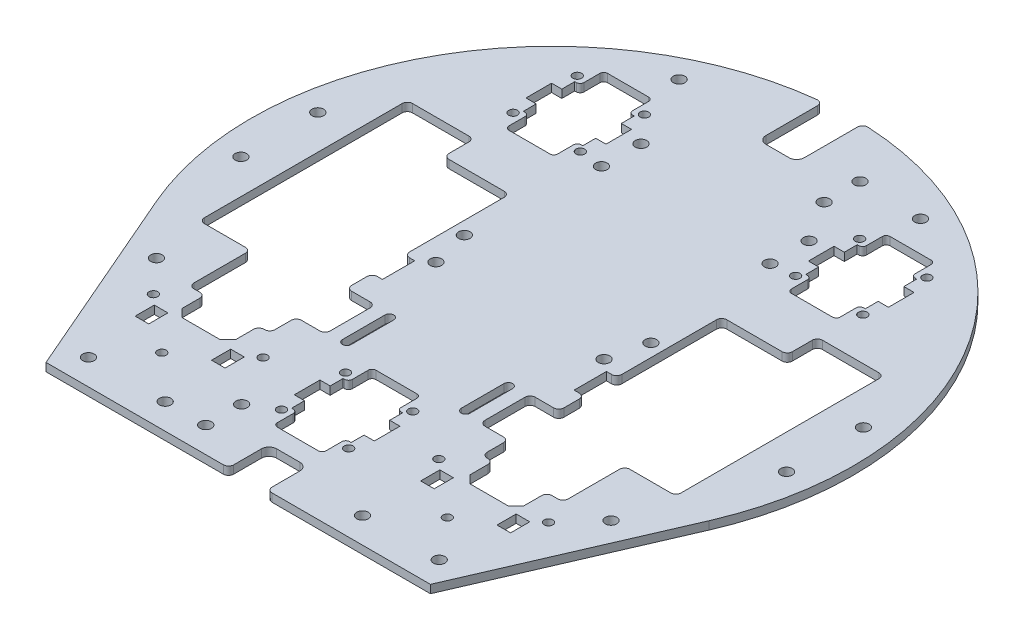
SolidWorks part; units mm, degrees
ref_plane "Front Plane" through (0, 0, 0) normal (0, 0, 1) x (1, 0, 0)
ref_plane "Top Plane" through (0, 0, 0) normal (0, 1, 0) x (1, 0, 0)
ref_plane "Right Plane" through (0, 0, 0) normal (1, 0, 0) x (0, 0, -1)
sketch "Sketch1" plane through (0, 0, 0) normal (0, 1, 0) x (1, 0, 0)
  circle A0 centre (0, 0) radius 117.5
  dimension "D1" = 235
extrude "Boss-Extrude1" add sketch "Sketch1" along normal blind 3.175
sketch "Sketch3" plane through (0, 0, 0) normal (0, 1, 0) x (1, 0, 0)
  line L3 (-107.8261, -46.6881) -> (-75, -122.5)
  line L5 (-75, -122.5) -> (75, -122.5)
  line L6 (75, -122.5) -> (107.8261, -46.6881)
  line L7 (107.8261, -46.6881) -> (-107.8261, -46.6881)
  line L8 (0, -122.5) -> (0, -117.5) construction
  circle A2 centre (0, 0) radius 117.5 construction
  dimension "D1" = 150
  dimension "D2" = 5
extrude "Boss-Extrude2" add sketch "Sketch3" along normal up to surface (3.175 mm away) up to face at (0, 3.175, 117.5)
sketch "Sketch4" plane through (0, 3.175, 0) normal (0, 1, 0) x (1, 0, 0)
  line L0 (70, 31.499) -> (70, -36.6986)
  line L1 (90, 31.499) -> (90, -36.6986)
  line L4 (93, 36.499) -> (67, 36.499)
  line L5 (90, -36.6986) -> (70, -36.6986) construction
  line L6 (67, 36.499) -> (67, 24.7405)
  line L7 (70, 31.499) -> (90, 31.499)
  line L8 (67, 24.7405) -> (41.4, 24.7405)
  line L9 (41.4, 24.7405) -> (41.4, -68.7747)
  line L10 (41.4, -68.7747) -> (73, -68.7747)
  line L11 (73, -68.7747) -> (73, -44.6986)
  line L12 (73, -44.6986) -> (93, -44.6986)
  line L13 (93, -44.6986) -> (93, 36.499)
  line L14 (46.4, 31.499) -> (89.2885, 31.499) construction
  line L15 (70, 31.499) -> (90, 31.499) construction
  line L19 (90, 31.499) -> (90, -36.6986) construction
  line L20 (70, 31.499) -> (70, -36.6986) construction
  line L22 (33.2, -41.8146) -> (33.2, -55.4255)
  line L24 (43.4, -41.8146) -> (33.2, -41.8146)
  line L25 (0, 0) -> (0, 30.6953) construction
  line L26 (-93, -44.6986) -> (-93, 36.499)
  line L27 (-73, -44.6986) -> (-93, -44.6986)
  line L28 (-73, -68.7747) -> (-73, -44.6986)
  line L29 (-41.4, -68.7747) -> (-73, -68.7747)
  line L30 (-41.4, 24.7405) -> (-41.4, -68.7747)
  line L31 (-67, 24.7405) -> (-41.4, 24.7405)
  line L32 (-67, 36.499) -> (-67, 24.7405)
  line L33 (-93, 36.499) -> (-67, 36.499)
  line L35 (33.2, -55.4255) -> (43.4, -55.4255) construction
  line L36 (39.4, -26.8239) -> (39.4, -18.2172)
  line L37 (39.4, -26.8239) -> (43.4, -26.8239)
  line L38 (43.4, -18.2172) -> (39.4, -18.2172)
  line L39 (68, 19.7405) -> (68, -67.7747)
  line L40 (68, -67.7747) -> (43.4, -67.7747)
  line L41 (43.4, 19.7405) -> (68, 19.7405)
  line L42 (43.4, 19.7405) -> (43.4, -18.2172)
  line L43 (43.4, -26.8239) -> (43.4, -41.8146)
  line L44 (43.4, -55.4255) -> (43.4, -67.7747)
  line L45 (43.4, -55.4255) -> (43.4, -67.7747) construction
  line L46 (43.4, -26.8239) -> (43.4, -41.8146) construction
  line L47 (43.4, 19.7405) -> (43.4, -18.2172) construction
  line L48 (43.4, 19.7405) -> (68, 19.7405) construction
  line L49 (68, -67.7747) -> (43.4, -67.7747) construction
  line L50 (68, 19.7405) -> (68, -67.7747) construction
  line L51 (43.4, -18.2172) -> (39.4, -18.2172) construction
  line L52 (39.4, -26.8239) -> (43.4, -26.8239) construction
  line L53 (39.4, -26.8239) -> (39.4, -18.2172) construction
  line L55 (43.4, -41.8146) -> (33.2, -41.8146) construction
  line L56 (33.2, -41.8146) -> (33.2, -55.4255) construction
  line L60 (33.2, -55.4255) -> (43.4, -55.4255)
  line L64 (90, -36.6986) -> (70, -36.6986)
  dimension "D1" = 2
  dimension "D2" = 5
  dimension "D3" = 5
  dimension "D4" = 8
  dimension "D5" = 3
  dimension "D6" = 5
  dimension "D7" = 5
  dimension "D8" = 3
  dimension "D9" = 2
extrude "Cut-Extrude1" cut sketch "Sketch4" against normal through all
sketch "Sketch8" plane through (0, 0, 0) normal (0, -1, 0) x (1, 0, 0)
  line L0 (-42, -78) -> (-68.225, -78) construction
  line L1 (13.1125, 12.5) -> (-13.1125, 12.5)
  line L2 (13.1125, 12.5) -> (13.1125, -12.5)
  line L3 (13.1125, -12.5) -> (-13.1125, -12.5)
  line L4 (-13.1125, 12.5) -> (-13.1125, -12.5)
  line L5 (13.1125, 12.5) -> (-13.1125, -12.5) construction
  line L6 (13.1125, -12.5) -> (-13.1125, 12.5) construction
  line L7 (-42, -53) -> (-42, -78) construction
  line L13 (0, 0) -> (0, -77.7063) construction
  line L14 (0, 80) -> (0, 0) construction
  line L15 (-42, -53) -> (-68.225, -53)
  line L16 (-42, -53) -> (-42, -78)
  line L17 (-42, -78) -> (-68.225, -78)
  line L18 (-68.225, -53) -> (-68.225, -78)
  line L19 (-42, -53) -> (-68.225, -78) construction
  line L20 (-42, -78) -> (-68.225, -53) construction
  line L21 (13.1125, 92.5) -> (-13.1125, 92.5)
  line L22 (13.1125, 92.5) -> (13.1125, 67.5)
  line L23 (13.1125, 67.5) -> (-13.1125, 67.5)
  line L24 (-13.1125, 92.5) -> (-13.1125, 67.5)
  line L25 (13.1125, 92.5) -> (-13.1125, 67.5) construction
  line L26 (13.1125, 67.5) -> (-13.1125, 92.5) construction
  line L27 (-42, -53) -> (-68.225, -53) construction
  line L28 (42, -78) -> (68.225, -78)
  line L29 (68.225, -53) -> (68.225, -78)
  line L30 (42, -78) -> (68.225, -53) construction
  line L31 (42, -53) -> (68.225, -78) construction
  line L32 (42, -53) -> (68.225, -53)
  line L33 (42, -53) -> (42, -78)
  point P0 (0, 0)
  point P15 (-55.1125, -65.5)
  point P20 (0, 80)
  point P29 (55.1125, -65.5)
  dimension "D1" = 42
  dimension "D2" = 80
hole_wizard "M3 Clearance Hole1" positions "Sketch9" profile "Sketch10" hole size "M3" standard "ANSI Metric" end condition through all
sketch "Sketch9" plane through (0, 3.175, 0) normal (0, 1, 0) x (1, 0, 0)
  point P0 (-68.225, 78)
  point P3 (-68.225, 53)
  point P6 (-42, 53)
  point P9 (-42, 78)
  point P12 (42, 78)
  point P15 (68.225, 78)
  point P18 (68.225, 53)
  point P21 (42, 53)
  point P24 (-13.1125, -67.5)
  point P27 (13.1125, -67.5)
  point P30 (13.1125, -92.5)
  point P33 (-13.1125, -92.5)
sketch "Sketch10" plane through (-68.225, 3.175, -78) normal (1, 0, 0) x (0, 0, 1)
  line L0 (0, 0) -> (0, 3.175)
  line L1 (0, 3.175) -> (1.7, 3.175)
  line L2 (1.7, 3.175) -> (1.7, 0)
  line L5 (1.7, 0) -> (0, 0)
  line L11 (0, -6.35) -> (0, 107.95) construction
  dimension "Thru Hole Dia." = 3.4
  dimension "Thru Hole Depth" = 3.175
sketch "Sketch11" plane through (0, 0, 0) normal (0, -1, 0) x (1, 0, 0)
  line L0 (47.6125, -48.2591) -> (62.6125, -48.2591)
  line L1 (62.6125, -82.7409) -> (47.6125, -82.7409)
  line L2 (62.6125, -82.7409) -> (47.6125, -82.7409)
  line L3 (47.6125, -48.2591) -> (62.6125, -48.2591)
  line L4 (-62.6125, -48.2591) -> (-47.6125, -48.2591)
  line L5 (-47.6125, -82.7409) -> (-62.6125, -82.7409)
  line L6 (-47.6125, -82.7409) -> (-62.6125, -82.7409)
  line L7 (-62.6125, -48.2591) -> (-47.6125, -48.2591)
  line L8 (-7.5, 97.2409) -> (7.5, 97.2409)
  line L9 (7.5, 62.7591) -> (-7.5, 62.7591)
  line L10 (7.5, 62.7591) -> (-7.5, 62.7591)
  line L11 (-7.5, 97.2409) -> (7.5, 97.2409)
sketch "Sketch12" plane through (0, 3.175, 0) normal (0, 1, 0) x (1, 0, 0)
  line L1 (-62.6125, 48.2591) -> (-47.6125, 48.2591) construction
  line L2 (-62.6125, 48.2591) -> (-62.6125, 82.7409) construction
  line L3 (-62.6125, 82.7409) -> (-47.6125, 82.7409) construction
  line L4 (-47.6125, 48.2591) -> (-47.6125, 82.7409) construction
  line L5 (47.6125, 48.2591) -> (62.6125, 48.2591) construction
  line L6 (47.6125, 48.2591) -> (47.6125, 82.7409) construction
  line L7 (47.6125, 82.7409) -> (62.6125, 82.7409) construction
  line L8 (62.6125, 48.2591) -> (62.6125, 82.7409) construction
  line L9 (-64.6125, 46.2591) -> (-45.6125, 46.2591)
  line L10 (-7.5, -97.2409) -> (7.5, -97.2409) construction
  line L11 (-7.5, -97.2409) -> (-7.5, -62.7591) construction
  line L12 (-7.5, -62.7591) -> (7.5, -62.7591) construction
  line L13 (7.5, -97.2409) -> (7.5, -62.7591) construction
  line L14 (-45.6125, 46.2591) -> (-45.6125, 84.7409)
  line L15 (-64.6125, 84.7409) -> (-45.6125, 84.7409)
  line L16 (-64.6125, 46.2591) -> (-64.6125, 84.7409)
  line L17 (45.6125, 46.2591) -> (64.6125, 46.2591)
  line L18 (64.6125, 46.2591) -> (64.6125, 84.7409)
  line L19 (45.6125, 84.7409) -> (64.6125, 84.7409)
  line L20 (45.6125, 46.2591) -> (45.6125, 84.7409)
  line L21 (-9.5, -99.2409) -> (9.5, -99.2409)
  line L22 (9.5, -99.2409) -> (9.5, -60.7591)
  line L23 (-9.5, -60.7591) -> (9.5, -60.7591)
  line L24 (-9.5, -99.2409) -> (-9.5, -60.7591)
  dimension "D1" = 2
extrude "Cut-Extrude3" cut sketch "Sketch12" against normal through all
sketch "Sketch13" plane through (0, 0, 0) normal (0, -1, 0) x (1, 0, 0)
  line L0 (-66.225, -75.0394) -> (-63.6125, -75.0394)
  line L1 (-63.6125, -55.9606) -> (-66.225, -55.9606)
  line L2 (-63.6125, -55.9606) -> (-66.225, -55.9606)
  line L3 (-66.225, -75.0394) -> (-63.6125, -75.0394)
  line L4 (-46.6125, -75.0394) -> (-44, -75.0394)
  line L5 (-44, -55.9606) -> (-46.6125, -55.9606)
  line L6 (-44, -55.9606) -> (-46.6125, -55.9606)
  line L7 (-46.6125, -75.0394) -> (-44, -75.0394)
  line L8 (63.6125, -75.0394) -> (66.225, -75.0394)
  line L9 (66.225, -55.9606) -> (63.6125, -55.9606)
  line L10 (66.225, -55.9606) -> (63.6125, -55.9606)
  line L11 (63.6125, -75.0394) -> (66.225, -75.0394)
  line L12 (44, -75.0394) -> (46.6125, -75.0394)
  line L13 (46.6125, -55.9606) -> (44, -55.9606)
  line L14 (46.6125, -55.9606) -> (44, -55.9606)
  line L15 (44, -75.0394) -> (46.6125, -75.0394)
  line L16 (8.5, 70.4606) -> (11.1125, 70.4606)
  line L17 (11.1125, 89.5394) -> (8.5, 89.5394)
  line L18 (11.1125, 89.5394) -> (8.5, 89.5394)
  line L19 (8.5, 70.4606) -> (11.1125, 70.4606)
  line L20 (-11.1125, 70.4606) -> (-8.5, 70.4606)
  line L21 (-8.5, 89.5394) -> (-11.1125, 89.5394)
  line L22 (-8.5, 89.5394) -> (-11.1125, 89.5394)
  line L23 (-11.1125, 70.4606) -> (-8.5, 70.4606)
sketch "Sketch14" plane through (0, 3.175, 0) normal (0, 1, 0) x (1, 0, 0)
  line L0 (-66.725, 55.4606) -> (-43.5, 55.4606)
  line L1 (-66.225, 55.9606) -> (-44, 55.9606) construction
  line L2 (-66.225, 55.9606) -> (-66.225, 75.0394) construction
  line L3 (-66.225, 75.0394) -> (-44, 75.0394) construction
  line L4 (-44, 55.9606) -> (-44, 75.0394) construction
  line L5 (44, 55.9606) -> (66.225, 55.9606) construction
  line L6 (44, 55.9606) -> (44, 75.0394) construction
  line L7 (44, 75.0394) -> (66.225, 75.0394) construction
  line L8 (66.225, 55.9606) -> (66.225, 75.0394) construction
  line L9 (-11.1125, -89.5394) -> (11.1125, -89.5394) construction
  line L10 (-11.1125, -89.5394) -> (-11.1125, -70.4606) construction
  line L11 (-11.1125, -70.4606) -> (11.1125, -70.4606) construction
  line L12 (11.1125, -89.5394) -> (11.1125, -70.4606) construction
  line L13 (-43.5, 55.4606) -> (-43.5, 75.5394)
  line L14 (-66.725, 75.5394) -> (-43.5, 75.5394)
  line L15 (-66.725, 55.4606) -> (-66.725, 75.5394)
  line L16 (43.5, 55.4606) -> (66.725, 55.4606)
  line L17 (66.725, 55.4606) -> (66.725, 75.5394)
  line L18 (43.5, 75.5394) -> (66.725, 75.5394)
  line L19 (43.5, 55.4606) -> (43.5, 75.5394)
  line L20 (-11.6125, -90.0394) -> (11.6125, -90.0394)
  line L21 (11.6125, -90.0394) -> (11.6125, -69.9606)
  line L22 (-11.6125, -69.9606) -> (11.6125, -69.9606)
  line L23 (-11.6125, -90.0394) -> (-11.6125, -69.9606)
  dimension "D1" = 0.5
extrude "Cut-Extrude4" cut sketch "Sketch14" against normal through all
sketch "Sketch15" plane through (0, 3.175, 0) normal (0, 1, 0) x (1, 0, 0)
  line L0 (-66.725, 75.5394) -> (-66.725, 55.4606) construction
  line L1 (-70.725, 60.5) -> (-39.5, 60.5)
  line L2 (-70.725, 60.5) -> (-70.725, 70.5)
  line L3 (-70.725, 70.5) -> (-39.5, 70.5)
  line L4 (-39.5, 60.5) -> (-39.5, 70.5)
  line L5 (-70.725, 60.5) -> (-39.5, 70.5) construction
  line L6 (-70.725, 70.5) -> (-39.5, 60.5) construction
  line L7 (39.5, 60.5) -> (70.725, 60.5)
  line L8 (39.5, 60.5) -> (39.5, 70.5)
  line L9 (39.5, 70.5) -> (70.725, 70.5)
  line L10 (70.725, 60.5) -> (70.725, 70.5)
  line L11 (39.5, 60.5) -> (70.725, 70.5) construction
  line L12 (39.5, 70.5) -> (70.725, 60.5) construction
  line L13 (-15.6125, -85) -> (15.6125, -85)
  line L14 (-15.6125, -85) -> (-15.6125, -75)
  line L15 (-15.6125, -75) -> (15.6125, -75)
  line L16 (15.6125, -85) -> (15.6125, -75)
  line L17 (-15.6125, -85) -> (15.6125, -75) construction
  line L18 (-15.6125, -75) -> (15.6125, -85) construction
  point P0 (-55.1125, 65.5)
  point P5 (55.1125, 65.5)
  point P11 (0, -80)
  dimension "D1" = 4
  dimension "D2" = 10
extrude "Cut-Extrude5" cut sketch "Sketch15" against normal through all
sketch "Sketch16" plane through (0, 0, 0) normal (0, -1, 0) x (1, 0, 0)
  line L4 (-5.225, -101.6482) -> (-2.225, -101.6482) construction
  line L5 (-2.225, -97.6482) -> (-5.225, -97.6482) construction
  line L6 (2.225, 112.6982) -> (5.225, 112.6982) construction
  line L7 (5.225, 116.6982) -> (2.225, 116.6982) construction
  line L8 (-3.775, 122.5) -> (-3.775, 109.6982)
  line L9 (-75, 122.5) -> (75, 122.5) construction
  line L10 (-0.775, 106.6982) -> (8.225, 106.6982)
  line L11 (11.225, 109.6982) -> (11.225, 122.5)
  line L12 (11.225, 122.5) -> (-3.775, 122.5)
  line L13 (3.725, 122.5) -> (3.725, 106.6982) construction
  line L14 (2.225, 114.6982) -> (5.225, 114.6982) construction
  line L15 (-11.225, -116.9626) -> (-11.225, -94.6482)
  line L16 (-8.225, -91.6482) -> (0.775, -91.6482)
  line L17 (3.775, -94.6482) -> (3.775, -117.4393)
  line L18 (-11.225, -94.6482) -> (3.775, -94.6482) construction
  line L19 (-3.725, -91.6482) -> (-3.725, -99.6482) construction
  line L20 (-2.225, -99.6482) -> (-5.225, -99.6482) construction
  arc A4 (-5.225, -97.6482) -> (-5.225, -101.6482) centre (-5.225, -99.6482) ccw construction
  arc A5 (-2.225, -101.6482) -> (-2.225, -97.6482) centre (-2.225, -99.6482) ccw construction
  arc A6 (5.225, 112.6982) -> (5.225, 116.6982) centre (5.225, 114.6982) ccw construction
  arc A7 (2.225, 116.6982) -> (2.225, 112.6982) centre (2.225, 114.6982) ccw construction
  arc A8 (-3.775, 109.6982) -> (-0.775, 106.6982) centre (-0.775, 109.6982) ccw
  arc A9 (8.225, 106.6982) -> (11.225, 109.6982) centre (8.225, 109.6982) ccw
  arc A10 (-107.8261, 46.6881) -> (107.8261, 46.6881) centre (0, 0) ccw construction
  arc A11 (-11.225, -94.6482) -> (-8.225, -91.6482) centre (-8.225, -94.6482) cw
  arc A12 (0.775, -91.6482) -> (3.775, -94.6482) centre (0.775, -94.6482) cw
  arc A13 (-11.225, -116.9626) -> (3.775, -117.4393) centre (0, 0) ccw
  point P26 (3.725, 114.6982)
  point P37 (-3.725, -99.6482)
  dimension "D1" = 8
  dimension "D3" = 3
  dimension "D4" = 8
  dimension "D2" = 15
extrude "Cut-Extrude6" cut sketch "Sketch16" against normal through all
fillet "Fillet1" radius 2 4 edges at (3.775, 1.5875, -117.4393) (-11.225, 1.5875, -116.9626) (11.225, 1.5875, 122.5) (-3.775, 1.5875, 122.5)
hole_wizard "#8 Clearance Hole1" positions "Sketch17" profile "Sketch18" hole size "#8" standard "ANSI Inch" end condition through all
sketch "Sketch17" plane through (0, 0, 0) normal (0, 1, 0) x (1, 0, 0)
  circle A0 centre (-88.6902, -65.7156) radius 1.7272 construction
  circle A1 centre (-106.4483, -15) radius 1.7272 construction
  circle A2 centre (-106.4483, 15) radius 1.7272 construction
  circle A3 centre (32.8, 67.45) radius 1.7272 construction
  circle A4 centre (32.9, 52.1319) radius 1.7272 construction
  circle A5 centre (36.4, 2.1319) radius 1.7272 construction
  circle A6 centre (32.8, -12.55) radius 1.7272 construction
  circle A7 centre (-32.8, -12.55) radius 1.7272 construction
  circle A8 centre (-36.4, 2.1319) radius 1.7272 construction
  circle A9 centre (-32.9, 52.1319) radius 1.7272 construction
  circle A10 centre (-32.8, 67.45) radius 1.7272 construction
  circle A11 centre (-47.0917, 96.6365) radius 1.7272 construction
  circle A12 centre (47.0917, 96.6365) radius 1.7272 construction
  circle A13 centre (106.4483, 15) radius 1.7272 construction
  circle A14 centre (106.4483, -15) radius 1.7272 construction
  circle A15 centre (88.6902, -65.7156) radius 1.7272 construction
  circle A16 centre (38.5, -112.5) radius 1.7272 construction
  circle A19 centre (-38.5, -112.5) radius 1.7272 construction
  circle A20 centre (-68.4328, -112.5) radius 1.7272 construction
  circle A21 centre (-88.6902, -65.7156) radius 1.7272
  circle A22 centre (-106.4483, -15) radius 1.7272
  circle A23 centre (-106.4483, 15) radius 1.7272
  circle A24 centre (32.8, 67.45) radius 1.7272
  circle A25 centre (32.9, 52.1319) radius 1.7272
  circle A26 centre (36.4, 2.1319) radius 1.7272
  circle A27 centre (32.8, -12.55) radius 1.7272
  circle A28 centre (-32.8, -12.55) radius 1.7272
  circle A29 centre (-36.4, 2.1319) radius 1.7272
  circle A30 centre (-32.9, 52.1319) radius 1.7272
  circle A31 centre (-32.8, 67.45) radius 1.7272
  circle A32 centre (-47.0917, 96.6365) radius 1.7272
  circle A33 centre (47.0917, 96.6365) radius 1.7272
  circle A34 centre (106.4483, 15) radius 1.7272
  circle A35 centre (106.4483, -15) radius 1.7272
  circle A36 centre (88.6902, -65.7156) radius 1.7272
  circle A37 centre (38.5, -112.5) radius 1.7272
  circle A38 centre (-22.6638, -98.5) radius 1.7272
  circle A39 centre (-22.6638, -112.5) radius 1.7272
  circle A40 centre (-38.5, -112.5) radius 1.7272
  circle A41 centre (-68.4328, -112.5) radius 1.7272
  circle A42 centre (68.4328, -112.5) radius 1.7272 construction
  circle A43 centre (68.4328, -112.5) radius 1.7272
  circle A45 centre (22.6638, 83.45) radius 1.7272
  circle A47 centre (22.6638, 97.45) radius 1.7272
  circle A48 centre (22.6638, 83.45) radius 1.7272 construction
  circle A49 centre (22.6638, 97.45) radius 1.7272 construction
  circle A50 centre (-22.6638, -98.5) radius 1.7272 construction
  circle A51 centre (-22.6638, -112.5) radius 1.7272 construction
  point P1 (-88.6902, -65.7156)
  point P3 (-106.4483, -15)
  point P5 (-106.4483, 15)
  point P7 (32.8, 67.45)
  point P9 (32.9, 52.1319)
  point P11 (36.4, 2.1319)
  point P13 (32.8, -12.55)
  point P15 (-32.8, -12.55)
  point P17 (-36.4, 2.1319)
  point P19 (-32.9, 52.1319)
  point P21 (-32.8, 67.45)
  point P23 (-47.0917, 96.6365)
  point P25 (47.0917, 96.6365)
  point P27 (106.4483, 15)
  point P29 (106.4483, -15)
  point P31 (88.6902, -65.7156)
  point P33 (38.5, -112.5)
  point P35 (-22.6638, -98.5)
  point P37 (-22.6638, -112.5)
  point P39 (-38.5, -112.5)
  point P41 (-68.4328, -112.5)
  point P109 (68.4328, -112.5)
  point P116 (22.6638, 83.45)
  point P119 (22.6638, 97.45)
sketch "Sketch18" plane through (-88.6902, 0, 65.7156) normal (1, 0, 0) x (0, 0, -1)
  line L0 (0, 0) -> (0, 3.175)
  line L1 (0, 3.175) -> (2.2479, 3.175)
  line L2 (2.2479, 3.175) -> (2.2479, 0)
  line L5 (2.2479, 0) -> (0, 0)
  line L11 (0, -6.35) -> (0, 107.95) construction
  dimension "Thru Hole Dia." = 4.4958
  dimension "Thru Hole Depth" = 3.175
hole_wizard "M3 Clearance Hole2" positions "Sketch19" profile "Sketch20" hole size "M3" standard "ANSI Metric" end condition through all
sketch "Sketch19" plane through (0, 0, 0) normal (0, -1, 0) x (-1, 0, 0)
  circle A1 centre (77.1, -78.5087) radius 1.8
  circle A2 centre (-77.1, -78.5087) radius 1.8 construction
  circle A3 centre (-55.7, -96.6207) radius 1.8 construction
  circle A4 centre (-34.3, -78.5087) radius 1.8 construction
  circle A7 centre (-77.1, -78.5087) radius 1.8
  circle A8 centre (-55.7, -96.6207) radius 1.8
  circle A9 centre (-34.3, -78.5087) radius 1.8
  circle A10 centre (34.3, -78.5087) radius 1.8
  circle A11 centre (55.7, -96.6207) radius 1.8
  circle A12 centre (55.7, -96.6207) radius 1.8 construction
  circle A13 centre (77.1, -78.5087) radius 1.8 construction
  circle A14 centre (34.3, -78.5087) radius 1.8 construction
  point P1 (77.1, -78.5087)
  point P4 (-77.1, -78.5087)
  point P6 (-55.7, -96.6207)
  point P8 (-34.3, -78.5087)
  point P10 (34.3, -78.5087)
  point P12 (55.7, -96.6207)
sketch "Sketch20" plane through (-77.1, 0, 78.5087) normal (1, 0, 0) x (0, 0, -1)
  line L0 (0, 0) -> (0, 3.175)
  line L1 (0, 3.175) -> (1.7, 3.175)
  line L2 (1.7, 3.175) -> (1.7, 0)
  line L5 (1.7, 0) -> (0, 0)
  line L11 (0, -6.35) -> (0, 107.95) construction
  dimension "Thru Hole Dia." = 3.4
  dimension "Thru Hole Depth" = 3.175
sketch "Sketch22" plane through (0, 0, 0) normal (0, -1, 0) x (1, 0, 0)
  line L11 (64.7, 72.5637) -> (64.7, 76.0717) construction
  line L12 (55.319, 78.8177) -> (50.7, 78.8177) construction
  line L13 (47.7, 76.7927) -> (47.7, 71.8427) construction
  line L14 (64.7, 72.5637) -> (64.7, 76.0717) construction
  line L15 (55.319, 78.8177) -> (50.7, 78.8177) construction
  line L16 (47.7, 76.7927) -> (47.7, 71.8427) construction
  line L17 (41.4, 68.7747) -> (73, 68.7747) construction
  line L18 (47.7, 68.7747) -> (64.7, 68.7747) construction
  line L19 (47.7, 68.7747) -> (47.7, 78.8177) construction
  line L20 (47.7, 78.8177) -> (64.7, 78.8177) construction
  line L21 (64.7, 68.7747) -> (64.7, 78.8177) construction
  line L22 (45.7, 66.7747) -> (45.7, 77.8177)
  line L23 (48.7, 80.8177) -> (63.7, 80.8177)
  line L24 (66.7, 66.7747) -> (66.7, 77.8177)
  line L25 (45.7, 66.7747) -> (66.7, 66.7747)
  line L26 (45.7, 77.8177) -> (48.7, 80.8177)
  line L27 (63.7, 80.8177) -> (66.7, 77.8177)
  line L28 (45.7, 66.7747) -> (45.7, 80.8177) construction
  line L29 (45.7, 80.8177) -> (66.7, 80.8177) construction
  line L30 (66.7, 66.7747) -> (66.7, 80.8177) construction
  line L31 (45.7, 77.8177) -> (45.7, 80.8177) construction
  line L32 (45.7, 80.8177) -> (48.7, 80.8177) construction
  line L33 (66.7, 77.8177) -> (66.7, 80.8177) construction
  line L34 (66.7, 80.8177) -> (63.7, 80.8177) construction
  line L35 (0, 0) -> (0, 34.6023) construction
  line L36 (-45.7, 66.7747) -> (-66.7, 66.7747)
  line L37 (-45.7, 66.7747) -> (-45.7, 77.8177)
  line L38 (-45.7, 77.8177) -> (-48.7, 80.8177)
  line L39 (-48.7, 80.8177) -> (-63.7, 80.8177)
  line L40 (-63.7, 80.8177) -> (-66.7, 77.8177)
  line L41 (-66.7, 66.7747) -> (-66.7, 77.8177)
  dimension "D1" = 2
  dimension "D2" = 3
extrude "Cut-Extrude8" cut sketch "Sketch22" against normal through all
fillet "Fillet4" radius 1.5 24 edges at (45.6125, 1.5875, -75.5394) (64.6125, 1.5875, -75.5394) (64.6125, 1.5875, -55.4606) (45.6125, 1.5875, -55.4606) (64.6125, 1.5875, -46.2591) (64.6125, 1.5875, -84.7409) (45.6125, 1.5875, -84.7409) (45.6125, 1.5875, -46.2591) (-64.6125, 1.5875, -46.2591) (-45.6125, 1.5875, -46.2591) (-45.6125, 1.5875, -84.7409) (-64.6125, 1.5875, -84.7409) (-64.6125, 1.5875, -75.5394) (-64.6125, 1.5875, -55.4606) (-45.6125, 1.5875, -55.4606) (-45.6125, 1.5875, -75.5394) (-9.5, 1.5875, 69.9606) (-9.5, 1.5875, 60.7591) (9.5, 1.5875, 60.7591) (9.5, 1.5875, 69.9606) (9.5, 1.5875, 90.0394) (-9.5, 1.5875, 99.2409) (9.5, 1.5875, 99.2409) (-9.5, 1.5875, 90.0394)
sketch "Sketch29" plane through (0, 3.175, 0) normal (0, 1, 0) x (1, 0, 0)
  line L14 (43.4, -28.8239) -> (43.4, -16.2172)
  line L17 (37.4, -28.8239) -> (43.4, -28.8239)
  line L18 (37.4, -16.2172) -> (37.4, -28.8239)
  line L19 (43.4, -16.2172) -> (37.4, -16.2172)
  line L20 (37.4, -28.8239) -> (43.4, -28.8239)
  line L21 (37.4, -16.2172) -> (37.4, -28.8239)
  line L22 (43.4, -16.2172) -> (37.4, -16.2172)
  line L28 (0, 0) -> (0, -34.7576) construction
  line L40 (-37.4, -16.2172) -> (-37.4, -28.8239)
  line L41 (-43.4, -16.2172) -> (-37.4, -16.2172)
  line L42 (-43.4, -28.8239) -> (-43.4, -16.2172)
  line L43 (-37.4, -28.8239) -> (-43.4, -28.8239)
  line L47 (43.4, -38.8146) -> (43.4, -58.4255)
  line L48 (-43.4, -38.8146) -> (-30.2, -38.8146)
  line L49 (-30.2, -38.8146) -> (-30.2, -58.4255)
  line L50 (30.2, -58.4255) -> (43.4, -58.4255)
  line L51 (30.2, -38.8146) -> (30.2, -58.4255)
  line L52 (43.4, -38.8146) -> (30.2, -38.8146)
  line L53 (30.2, -58.4255) -> (43.4, -58.4255)
  line L54 (30.2, -38.8146) -> (30.2, -58.4255)
  line L55 (43.4, -38.8146) -> (30.2, -38.8146)
  line L56 (-30.2, -58.4255) -> (-43.4, -58.4255)
  line L57 (-43.4, -38.8146) -> (-43.4, -58.4255)
  dimension "D2" = 3
  dimension "D1" = 2
extrude "Cut-Extrude9" cut sketch "Sketch29" against normal through all
fillet "Fillet5" radius 2 16 edges at (30.2, 1.5875, 38.8146) (30.2, 1.5875, 58.4255) (41.4, 1.5875, 58.4255) (41.4, 1.5875, 38.8146) (41.4, 1.5875, 28.8239) (41.4, 1.5875, 16.2172) (41.4, 1.5875, -24.7405) (67, 1.5875, -24.7405) (67, 1.5875, -36.499) (93, 1.5875, -36.499) (93, 1.5875, 44.6986) (73, 1.5875, 44.6986) (73, 1.5875, 68.7747) (66.7, 1.5875, 68.7747) (41.4, 1.5875, 68.7747) (45.7, 1.5875, 68.7747)
fillet "Fillet6" radius 2 16 edges at (-41.4, 1.5875, 28.8239) (-41.4, 1.5875, 38.8146) (-30.2, 1.5875, 38.8146) (-30.2, 1.5875, 58.4255) (-41.4, 1.5875, 58.4255) (-73, 1.5875, 68.7747) (-73, 1.5875, 44.6986) (-93, 1.5875, 44.6986) (-67, 1.5875, -36.499) (-67, 1.5875, -24.7405) (-41.4, 1.5875, -24.7405) (-41.4, 1.5875, 16.2172) (-93, 1.5875, -36.499) (-45.7, 1.5875, 68.7747) (-41.4, 1.5875, 68.7747) (-66.7, 1.5875, 68.7747)
sketch "Sketch30" plane through (0, 0, 0) normal (0, -1, 0) x (1, 0, 0)
  line L0 (-73.1, 89.3177) -> (-73.1, 82.1333) construction
  line L1 (-73.1, 82.1333) -> (-68.1, 82.1333) construction
  line L2 (-68.1, 82.1333) -> (-68.1, 89.3177) construction
  line L3 (-68.1, 89.3177) -> (-73.1, 89.3177) construction
  line L4 (-38.3, 82.1333) -> (-38.3, 89.3177) construction
  line L5 (-38.3, 89.3177) -> (-43.3, 89.3177) construction
  line L6 (-43.3, 89.3177) -> (-43.3, 82.1333) construction
  line L7 (-43.3, 82.1333) -> (-38.3, 82.1333) construction
  line L8 (38.3, 89.3177) -> (38.3, 82.1333) construction
  line L9 (38.3, 82.1333) -> (43.3, 82.1333) construction
  line L10 (43.3, 82.1333) -> (43.3, 89.3177) construction
  line L11 (43.3, 89.3177) -> (38.3, 89.3177) construction
  line L12 (73.1, 82.1333) -> (73.1, 89.3177) construction
  line L13 (73.1, 89.3177) -> (68.1, 89.3177) construction
  line L14 (68.1, 89.3177) -> (68.1, 82.1333) construction
  line L15 (68.1, 82.1333) -> (73.1, 82.1333) construction
  line L16 (-73.1, 89.3177) -> (-73.1, 82.1333) construction
  line L17 (-73.1, 82.1333) -> (-68.1, 82.1333) construction
  line L18 (-68.1, 82.1333) -> (-68.1, 89.3177) construction
  line L19 (-68.1, 89.3177) -> (-73.1, 89.3177) construction
  line L20 (-38.3, 82.1333) -> (-38.3, 89.3177) construction
  line L21 (-38.3, 89.3177) -> (-43.3, 89.3177) construction
  line L22 (-43.3, 89.3177) -> (-43.3, 82.1333) construction
  line L23 (-43.3, 82.1333) -> (-38.3, 82.1333) construction
  line L24 (38.3, 89.3177) -> (38.3, 82.1333) construction
  line L25 (38.3, 82.1333) -> (43.3, 82.1333) construction
  line L26 (43.3, 82.1333) -> (43.3, 89.3177) construction
  line L27 (43.3, 89.3177) -> (38.3, 89.3177) construction
  line L28 (73.1, 82.1333) -> (73.1, 89.3177) construction
  line L29 (73.1, 89.3177) -> (68.1, 89.3177) construction
  line L30 (68.1, 89.3177) -> (68.1, 82.1333) construction
  line L31 (68.1, 82.1333) -> (73.1, 82.1333) construction
  line L32 (-73.25, 89.4677) -> (-73.25, 81.9833)
  line L33 (-73.25, 81.9833) -> (-67.95, 81.9833)
  line L34 (-67.95, 81.9833) -> (-67.95, 89.4677)
  line L35 (-67.95, 89.4677) -> (-73.25, 89.4677)
  line L36 (-38.15, 81.9833) -> (-38.15, 89.4677)
  line L37 (-38.15, 89.4677) -> (-43.45, 89.4677)
  line L38 (-43.45, 89.4677) -> (-43.45, 81.9833)
  line L39 (-43.45, 81.9833) -> (-38.15, 81.9833)
  line L40 (38.15, 89.4677) -> (38.15, 81.9833)
  line L41 (38.15, 81.9833) -> (43.45, 81.9833)
  line L42 (43.45, 81.9833) -> (43.45, 89.4677)
  line L43 (43.45, 89.4677) -> (38.15, 89.4677)
  line L44 (73.25, 81.9833) -> (73.25, 89.4677)
  line L45 (73.25, 89.4677) -> (67.95, 89.4677)
  line L46 (67.95, 89.4677) -> (67.95, 81.9833)
  line L47 (67.95, 81.9833) -> (73.25, 81.9833)
  dimension "D1" = 0.15
extrude "Cut-Extrude10" cut sketch "Sketch30" against normal through all
hole_wizard "M3 Clearance Slot1" positions "Sketch26" profile "Sketch24" size "M3" standard "ANSI Metric" slot yes end condition through all
sketch "Sketch26" plane through (0, 3.175, 0) normal (0, 1, 0) x (1, 0, 0)
  line L0 (23.2, -58.62) -> (23.2, -38.62) construction
  line L8 (23.2, -48.62) -> (30.2, -48.62)
  line L10 (30.2, -40.8146) -> (30.2, -56.4255) construction
  line L11 (0, 0) -> (0, -34.2526) construction
  point P0 (23.2, -48.62)
  point P35 (-23.2, -48.62)
  dimension "D1" = 20
  dimension "D2" = 7
sketch "Sketch24" plane through (23.2, 3.175, 48.62) normal (1, 0, 0) x (0, 0, 1)
  line L0 (0, 0) -> (0, 3.175)
  line L1 (0, 3.175) -> (1.7, 3.175)
  line L2 (1.7, 3.175) -> (1.7, 0)
  line L5 (1.7, 0) -> (0, 0)
  line L11 (0, -6.35) -> (0, 107.95) construction
  dimension "Thru Hole Dia." = 3.4
  dimension "Thru Hole Depth" = 3.175
